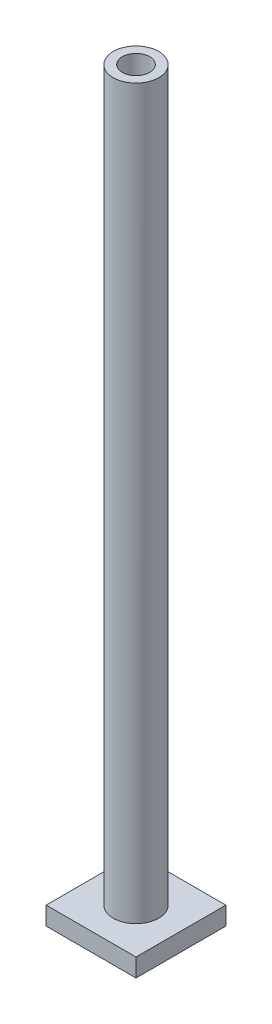
SolidWorks part; units mm, degrees
ref_plane "Front Plane" through (0, 0, 0) normal (0, 0, 1) x (1, 0, 0)
ref_plane "Top Plane" through (0, 0, 0) normal (0, 1, 0) x (1, 0, 0)
ref_plane "Right Plane" through (0, 0, 0) normal (1, 0, 0) x (0, 0, -1)
sketch "Sketch1" plane through (0, 0, 0) normal (0, 1, 0) x (1, 0, 0)
  line L1 (7.9, 7.9) -> (-7.9, 7.9)
  line L2 (7.9, 7.9) -> (7.9, -7.9)
  line L3 (7.9, -7.9) -> (-7.9, -7.9)
  line L4 (-7.9, 7.9) -> (-7.9, -7.9)
  line L5 (7.9, 7.9) -> (-7.9, -7.9) construction
  line L6 (7.9, -7.9) -> (-7.9, 7.9) construction
  point P0 (0, 0)
  dimension "D1" = 15.8
extrude "Base" add sketch "Sketch1" along normal blind 3.2
sketch "Sketch2" plane through (0, 0, 0) normal (0, -1, 0) x (1, 0, 0)
  line L0 (0, 6.6) -> (0, -6.6) construction
  line L1 (6.6, 6.6) -> (-6.6, 6.6)
  line L2 (6.6, 6.6) -> (6.6, -6.6)
  line L3 (6.6, -6.6) -> (-6.6, -6.6)
  line L4 (-6.6, 6.6) -> (-6.6, -6.6)
  line L5 (6.6, 6.6) -> (-6.6, -6.6) construction
  line L6 (6.6, -6.6) -> (-6.6, 6.6) construction
  line L7 (-6.6, 0) -> (6.6, 0) construction
  line L8 (-7.9, -7.9) -> (-7.9, 7.9) construction
  line L9 (0, -6.6) -> (0, -7.9) construction
  line L10 (7.9, -7.9) -> (-7.9, -7.9) construction
  line L12 (-1.25, -6.6) -> (1.25, -6.6)
  line L13 (-1.25, -6.6) -> (-1.25, -7.9)
  line L14 (-1.25, -7.9) -> (1.25, -7.9)
  line L15 (1.25, -6.6) -> (1.25, -7.9)
  line L16 (-1.25, -6.6) -> (1.25, -7.9) construction
  line L17 (-1.25, -7.9) -> (1.25, -6.6) construction
  line L18 (-1.25, -2.1651) -> (1.25, -2.1651)
  line L19 (-1.25, -2.1651) -> (-1.25, -6.6)
  line L20 (-1.25, -6.6) -> (1.25, -6.6)
  line L21 (1.25, -2.1651) -> (1.25, -6.6)
  circle A4 centre (0, 0) radius 3.4
  circle A5 centre (0, 0) radius 2.5
  point P0 (0, 0)
  point P6 (0, -7.25)
  line M4 (-7.9, -7.9) -> (7.9, -7.9)
  dimension "D4" = 5
  dimension "D2" = 1.3
  dimension "D5" = 0.9
  dimension "D1" = 2.5
extrude "Bottom cut" cut sketch "Sketch2" against normal offset from surface (2 mm away) 1.2 contours A4 L21 L3 L2 L1 L4 L19 | L18 A5 | L18 A5 | A5 L19 A4 L21 | A4 L19 L3 L21 | L15 L3 L13 M4 region at (6.4133, 0, 0) region at (0, 0, -7.25) region at (0, 0, -4.9601) region at (0, 0, -2.8541) region at (0, 0, -2.2998) region at (0, 0, 0.0683) up to face at (0, 3.2, 0)
sketch "Sketch3" plane through (0, 3.2, 0) normal (0, 1, 0) x (1, 0, 0)
  circle A0 centre (0, 0) radius 4
  circle A1 centre (0, 0) radius 2.4
  dimension "D1" = 8
  dimension "D2" = 1.6
extrude "Lamp post" add sketch "Sketch3" along normal blind 128
sketch "Sketch4" plane through (0, 3.2, 0) normal (0, 1, 0) x (1, 0, 0)
  circle A0 centre (0, 0) radius 2.4 construction
  circle A1 centre (0, 0) radius 2.4
extrude "Wire bottom cut" cut sketch "Sketch4" against normal up to next
equation "\"P\"= \"LegoUnit\" * 5"
equation "\"D1@Sketch1\" = \"BrickSize\" * 2 - \"Padding\""
equation "\"Padding\"= \"LegoUnit\" / 8"
equation "\"SmallHeight\"= \"LegoUnit\" * 2"
equation "\"LargeHight\"= \"LegoUnit\" * 6"
equation "\"D1@Base\" = \"SmallHeight\""
equation "\"InsetDiameter\"= \"LegoUnit\" * 2 - \"Padding\" * 3"
equation "\"LegoUnit\"=1.6"
equation "\"BrickSize\"= \"LegoUnit\" * 5"
equation "\"WallSize\" = \"LegoUnit\" - \"Padding\" * 1.5"
equation "\"D2@Sketch2\"=\"WallSize\""
equation "\"BumpSize\"= \"LegoUnit\" * 3"
equation "\"InsideBumpSize\"= \"BumpSize\" + \"Padding\""
equation "\"InnerWallSize\"= \"Padding\" * 4.5"
equation "\"D5@Sketch2\"=\"InnerWallSize\""
equation "\"CeilingSize\"= \"LegoUnit\" - \"Padding\" * 2"
equation "\"D1@Bottom cut\" = \"CeilingSize\""
equation "\"D4@Sketch2\"=\"InsideBumpSize\""
equation "\"D1@Sketch3\"=\"BrickSize\""
equation "\"D2@Sketch3\"=\"LegoUnit\""
equation "\"D1@Lamp post\"=\"SmallHeight\" * 40"
